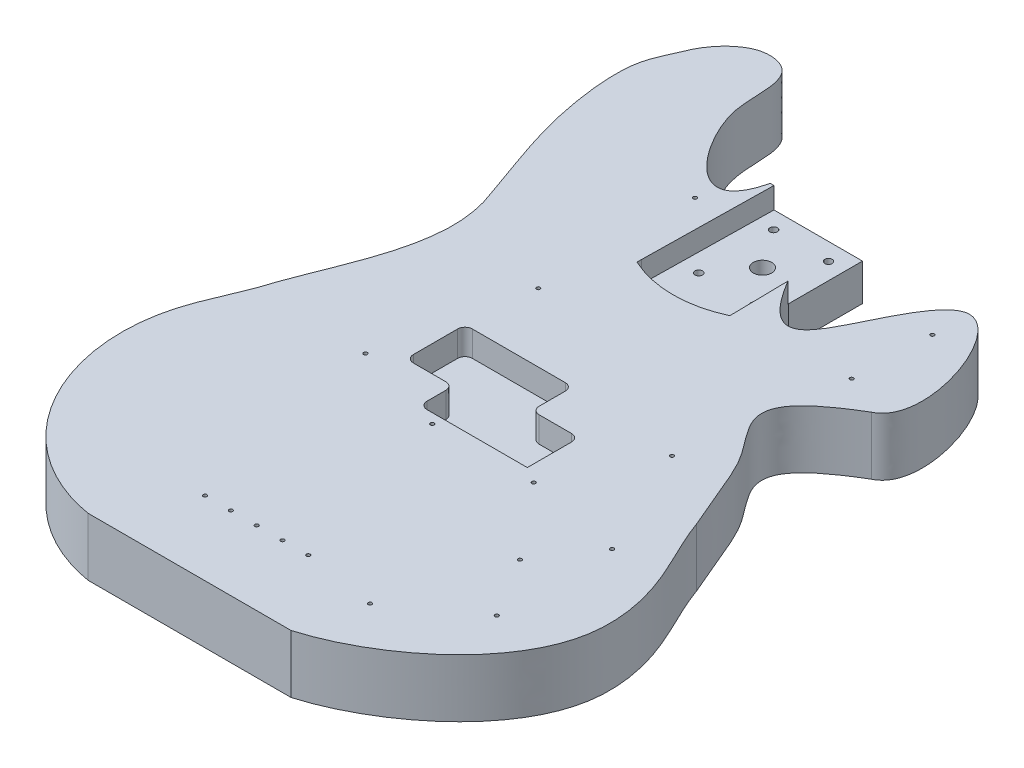
SolidWorks part; units mm, degrees
ref_plane "Front Plane" through (0, 0, 0) normal (0, 0, 1) x (1, 0, 0)
ref_plane "Top Plane" through (0, 0, 0) normal (0, 1, 0) x (1, 0, 0)
ref_plane "Right Plane" through (0, 0, 0) normal (1, 0, 0) x (0, 0, -1)
sketch "Sketch1" plane through (0, 0, 0) normal (0, 1, 0) x (1, 0, 0)
  line L0 (-31.75, 431.8) -> (31.75, 431.8)
  line L1 (-69.85, 0) -> (69.85, 0)
  line L2 (31.75, 431.8) -> (31.75, 381)
  line L3 (0, 431.8) -> (0, 0) construction
  spline S0 degree 3 poles (-69.85, 0) (-122.7459, 8.8946) (-170.3738, 68.3736) (-165.5312, 154.7593) (-147.8347, 185.8105) (-142.875, 203.2) knots 0 0 0 0 0.581043 0.783837 1 1 1 1
  spline S1 degree 3 poles (-142.875, 203.2) (-128.6398, 243.0991) (-104.4904, 285.9502) (-122.2248, 330.2) knots 0 0 0 0 1 1 1 1
  spline S2 degree 3 poles (-122.2248, 330.2) (-131.7635, 357.8566) (-146.2426, 392.3515) (-152.7726, 455.2781) (-144.5433, 471.0132) (-135.4704, 492.8612) (-120.6511, 508.7509) (-90.8297, 507.3178) (-88.3646, 481.7202) (-88.7047, 444.4419) (-43.0115, 384.6457) (-31.75, 431.8) knots 0 0 0 0 0.228271 0.373681 0.455315 0.473382 0.545352 0.564859 0.659458 0.744201 1 1 1 1
  spline S3 degree 3 poles (69.85, 0) (111.9348, 12.1111) (186.0145, 65.7497) (170.8416, 155.4983) (152.3381, 185.6263) (146.05, 203.2) knots 0 0 0 0 0.586136 0.784814 1 1 1 1
  spline S4 degree 3 poles (146.05, 203.2) (136.1599, 225.6504) (132.5896, 236.8474) (120.3836, 260.933) (109.5687, 273.3596) (96.5902, 297.0243) (109.0963, 311.9927) (139.7, 330.2) knots 0 0 0 0 0.33898 0.396393 0.554386 0.616722 1 1 1 1
  spline S5 degree 3 poles (139.7, 330.2) (166.4459, 342.892) (123.5038, 464.5308) (76.8127, 369.3895) (59.5093, 333.6668) (31.75, 381) knots 0 0 0 0 0.451982 0.679896 1 1 1 1
  point P5 (0, 412.75)
  point P7 (0, 0)
  point P10 (0, 50.8)
  point P11 (0, 101.6)
  point P12 (0, 152.4)
  point P13 (0, 177.8)
  point P15 (0, 203.2)
  point P17 (0, 254)
  point P18 (0, 279.4)
  point P19 (0, 330.2)
  point P20 (0, 406.4)
  point P21 (0, 381)
  point P22 (0, 482.6)
  point P23 (0, 508)
  point P24 (0, 457.2)
  point P25 (0, 355.6)
  point P38 (0, 422.275)
  dimension "D5" = 50.8
  dimension "D35" = 149.225
  dimension "D42" = 139.7
  dimension "D1" = 63.5
  dimension "D2" = 139.7
  dimension "D4" = 431.8
  dimension "D6" = 101.6
  dimension "D7" = 152.4
  dimension "D8" = 177.8
  dimension "D9" = 203.2
  dimension "D10" = 254
  dimension "D11" = 279.4
  dimension "D12" = 330.2
  dimension "D13" = 381
  dimension "D14" = 406.4
  dimension "D15" = 457.2
  dimension "D16" = 482.6
  dimension "D17" = 508
  dimension "D18" = 146.05
  dimension "D19" = 165.1
  dimension "D20" = 161.925
  dimension "D21" = 152.4
  dimension "D22" = 142.875
  dimension "D23" = 123.825
  dimension "D24" = 117.475
  dimension "D25" = 122.2248
  dimension "D26" = 139.7
  dimension "D27" = 146.05
  dimension "D28" = 149.225
  dimension "D29" = 139.7
  dimension "D30" = 107.95
  dimension "D31" = 88.9
  dimension "D32" = 85.725
  dimension "D33" = 6.35
  dimension "D34" = 53.975
  dimension "D36" = 174.625
  dimension "D37" = 168.275
  dimension "D38" = 157.1498
  dimension "D39" = 146.05
  dimension "D40" = 123.825
  dimension "D41" = 106.3498
  dimension "D43" = 355.6
  dimension "D44" = 422.275
  dimension "D45" = 146.05
  dimension "D46" = 114.3
  dimension "D47" = 82.55
  dimension "D48" = 66.675
extrude "Boss-Extrude1" add sketch "Sketch1" along normal blind 40.005
sketch "Sketch2" plane through (0, 40.005, 0) normal (0, 1, 0) x (1, 0, 0)
  line L0 (-29.21, 431.8) -> (31.75, 431.8)
  line L1 (31.75, 431.8) -> (-31.75, 431.8) construction
  line L2 (31.75, 381) -> (31.75, 431.8) construction
  line L3 (-29.21, 431.8) -> (-30.6832, 341.9475)
  line L4 (31.75, 431.8) -> (33.2232, 341.9475)
  line L5 (1.27, 431.8) -> (1.27, 340.7706) construction
  line L6 (-30.6832, 341.9475) -> (33.2232, 341.9475) construction
  line L7 (33.2232, 341.9475) -> (33.2232, 338.8995)
  line L8 (-30.6832, 341.9475) -> (-30.6832, 338.8995)
  line L9 (1.27, 407.1241) -> (1.27, 331.7875) construction
  arc A0 (-30.6832, 338.8995) -> (33.2232, 338.8995) centre (1.27, 407.1241) ccw
  point P13 (1.27, 341.9475)
  dimension "D5" = 7.112
  dimension "D1" = 60.96
  dimension "D2" = 89.8525
  dimension "D3" = 63.9064
  dimension "D4" = 3.048
extrude "Cut-Extrude1" cut sketch "Sketch2" against normal blind 14.605
sketch "Sketch3" plane through (0, 25.4, 0) normal (0, 1, 0) x (1, 0, 0)
  line L0 (1.27, 431.8) -> (1.27, 393.3952) construction
  line L1 (31.75, 431.8) -> (-29.21, 431.8) construction
  line L2 (31.75, 381) -> (31.75, 431.8) construction
  line L5 (33.2232, 341.9475) -> (32.6067, 379.5515) construction
  line L6 (-29.21, 431.8) -> (-30.6832, 341.9475) construction
  circle A0 centre (1.27, 393.3952) radius 6.35
  circle A1 centre (-17.526, 419.862) radius 2.54
  circle A2 centre (20.2692, 419.862) radius 2.54
  circle A3 centre (20.5972, 368.3) radius 2.54
  circle A4 centre (-17.5491, 368.3) radius 2.54
  point P0 (1.27, 399.7452)
  point P14 (-17.526, 422.402)
  point P15 (20.2692, 422.402)
  point P17 (22.8092, 419.862)
  point P19 (-14.986, 419.862)
  point P20 (23.1372, 368.3)
  point P21 (-20.0891, 368.3)
  point P22 (-17.5491, 370.84)
  point P23 (20.5972, 370.84)
  point P24 (-15.0091, 368.3)
  point P28 (18.0572, 368.3)
  dimension "D1" = 5.08
  dimension "D2" = 12.7
  dimension "D3" = 32.0548
  dimension "D4" = 9.398
  dimension "D5" = 8.9408
  dimension "D6" = 46.736
  dimension "D7" = 15.24
  dimension "D8" = 14.732
  dimension "D9" = 60.96
extrude "Cut-Extrude2" cut sketch "Sketch3" against normal through all
sketch "Sketch4" plane through (0, 40.005, 0) normal (0, 1, 0) x (1, 0, 0)
  line L0 (31.75, 431.8) -> (-29.21, 431.8) construction
  line L1 (-47.498, 242.316) -> (16.51, 242.316)
  line L2 (-52.578, 237.236) -> (-52.578, 206.756)
  line L3 (-47.498, 201.676) -> (-25.146, 201.676)
  line L4 (21.59, 237.236) -> (21.59, 219.202)
  line L5 (26.67, 214.122) -> (49.022, 214.122)
  line L6 (-20.066, 196.596) -> (-20.066, 183.642)
  line L7 (-14.986, 178.562) -> (54.102, 178.562)
  line L8 (54.102, 209.042) -> (54.102, 178.562)
  line L9 (31.75, 381) -> (31.75, 431.8) construction
  arc A0 (-20.066, 183.642) -> (-14.986, 178.562) centre (-14.986, 183.642) ccw
  arc A1 (49.022, 214.122) -> (54.102, 209.042) centre (49.022, 209.042) cw
  arc A2 (26.67, 214.122) -> (21.59, 219.202) centre (26.67, 219.202) cw
  arc A3 (-25.146, 201.676) -> (-20.066, 196.596) centre (-25.146, 196.596) cw
  arc A4 (-52.578, 206.756) -> (-47.498, 201.676) centre (-47.498, 206.756) ccw
  arc A5 (16.51, 242.316) -> (21.59, 237.236) centre (16.51, 237.236) cw
  arc A6 (-47.498, 242.316) -> (-52.578, 237.236) centre (-47.498, 237.236) ccw
  dimension "D7" = 5.08
  dimension "D1" = 35.56
  dimension "D2" = 74.168
  dimension "D3" = 63.754
  dimension "2.92" = 74.168
  dimension "D4" = 106.68
  dimension "D5" = 189.484
  dimension "D6" = 10.16
extrude "Cut-Extrude3" cut sketch "Sketch4" against normal blind 17.5514
sketch "Sketch5" plane through (0, 40.005, 0) normal (0, 1, 0) x (1, 0, 0)
  line L0 (-29.21, 431.8) -> (-30.6832, 341.9475) construction
  line L1 (16.51, 242.316) -> (-47.498, 242.316) construction
  line L2 (30.2922, 397.256) -> (30.2922, 83.7471) construction
  line L3 (-14.986, 178.562) -> (54.102, 178.562) construction
  circle A0 centre (-49.0828, 397.256) radius 1.27
  circle A1 centre (-49.0828, 289.306) radius 1.27
  circle A2 centre (-69.7203, 190.881) radius 1.27
  circle A3 centre (112.8422, 343.281) radius 1.27
  circle A4 centre (114.417, 397.256) radius 1.27
  circle A5 centre (96.9672, 235.331) radius 1.27
  circle A6 centre (131.8922, 159.131) radius 1.27
  circle A7 centre (131.8922, 79.756) radius 1.27
  circle A8 centre (81.0922, 43.2435) radius 1.27
  circle A9 centre (106.4922, 121.031) radius 1.27
  circle A10 centre (65.2172, 171.831) radius 1.27
  circle A11 centre (-40.1928, 50.8508) radius 1.27
  circle A12 centre (-22.4128, 50.8508) radius 1.27
  circle A13 centre (-4.6328, 50.8508) radius 1.27
  circle A14 centre (13.1472, 50.8508) radius 1.27
  circle A15 centre (30.9272, 50.8508) radius 1.27
  circle A16 centre (-4.6328, 171.831) radius 1.27
  point P2 (-47.8128, 397.256)
  point P5 (-49.0828, 395.986)
  point P42 (30.2922, 390.906)
  point P43 (30.2922, 365.506)
  point P44 (30.2922, 340.106)
  point P45 (30.2922, 314.706)
  point P46 (30.2922, 289.306)
  point P47 (30.2922, 263.906)
  point P48 (30.2922, 238.506)
  point P49 (30.2922, 213.106)
  point P50 (30.2922, 187.706)
  point P51 (30.2922, 162.306)
  point P52 (30.2922, 136.906)
  point P53 (30.2922, 111.506)
  point P54 (30.2922, 86.106)
  point P63 (-4.6328, 52.1208)
  dimension "D1" = 2.54
  dimension "D27" = 17.78
  dimension "D2" = 18.034
  dimension "D3" = 153.67
  dimension "D4" = 79.375
  dimension "D5" = 79.375
  dimension "D6" = 6.35
  dimension "D8" = 25.4
  dimension "D9" = 100.0125
  dimension "D10" = 3.175
  dimension "D11" = 34.925
  dimension "D12" = 9.525
  dimension "D13" = 69.85
  dimension "D14" = 41.275
  dimension "D15" = 76.2
  dimension "D16" = 50.8
  dimension "D17" = 119.0625
  dimension "D18" = 101.6
  dimension "D19" = 82.55
  dimension "D20" = 101.6
  dimension "D21" = 3.175
  dimension "D22" = 66.675
  dimension "D23" = 3.175
  dimension "D24" = 3.175
  dimension "D25" = 82.55
  dimension "D26" = 84.1248
  dimension "D28" = 35.56
  dimension "D29" = 53.34
  dimension "D30" = 71.12
  dimension "D31" = 126.4412
  dimension "D7" = 13
extrude "Cut-Extrude4" cut sketch "Sketch5" against normal blind 17.78
